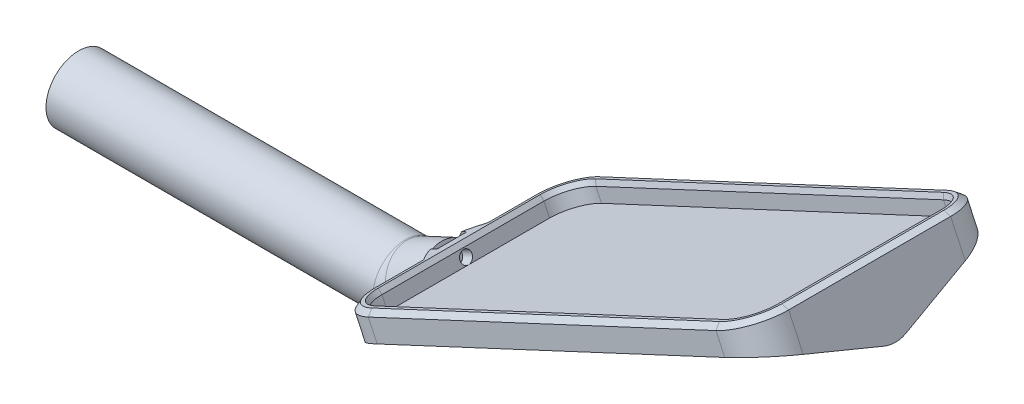
SolidWorks part; units mm, degrees
ref_plane "Alzado" through (0, 0, 0) normal (0, 0, 1) x (1, 0, 0)
ref_plane "Planta" through (0, 0, 0) normal (0, 1, 0) x (1, 0, 0)
ref_plane "Vista lateral" through (0, 0, 0) normal (1, 0, 0) x (0, 0, -1)
sketch "Croquis1" plane through (0, 0, 0) normal (1, 0, 0) x (0, 0, -1)
  circle A0 centre (0, 0) radius 9
  dimension "D1" = 18
extrude "Saliente-Extruir1" add sketch "Croquis1" along normal blind 90
sketch "Croquis2" plane through (90, 0, 0) normal (1, 0, 0) x (0, 0, -1)
  line L0 (-18.2788, 10) -> (25.9849, 10) construction
  circle A1 centre (0, 0) radius 9
  circle A2 centre (0, 0) radius 9
  dimension "D1" = 10
  dimension "D2" = 0
revolve "Revolución1" add sketch "Croquis2" angle 25 about L0 reverse direction yes
sketch "Croquis3" plane through (77.7557, 36.2581, 0) normal (0.9063, 0.4226, 0) x (0, 0, -1)
  circle A1 centre (0, -38.9726) radius 9
  circle A2 centre (0, -38.9726) radius 9
  dimension "D1" = 0
extrude "Saliente-Extruir2" add sketch "Croquis3" along normal blind 140
sketch "Croquis5" plane through (204.6388, 95.4246, 0) normal (0.9063, 0.4226, 0) x (0, 0, -1)
  line L0 (-32.8, -36.8226) -> (-3.0251, -47.4489)
  line L1 (-32.8, -29.8226) -> (32.8, -29.8226)
  line L2 (-32.8, -29.8226) -> (-32.8, -36.8226)
  line L4 (32.8, -29.8226) -> (32.8, -36.8226)
  line L5 (32.8, -36.8226) -> (3.0251, -47.4489)
  circle A1 centre (0, -38.9726) radius 9
  arc A2 (-3.0251, -47.4489) -> (3.0251, -47.4489) centre (0, -38.9726) ccw
  point P7 (0, -29.8226)
  dimension "D2" = 65.6
  dimension "D3" = 7
  dimension "D1" = 0
extrude "Saliente-Extruir3" add sketch "Croquis5" against normal blind 126.6
sketch "Croquis7" plane through (12.6036, -27.0285, 0) normal (-0.4226, 0.9063, 0) x (0.9063, 0.4226, 0)
  line L1 (102.1939, 29.8) -> (222.7939, 29.8)
  line L2 (102.1939, 29.8) -> (102.1939, -29.8)
  line L3 (102.1939, -29.8) -> (222.7939, -29.8)
  line L4 (222.7939, 29.8) -> (222.7939, -29.8)
  line L6 (99.1939, 9) -> (99.1939, -9) construction
  line L7 (99.1939, 32.8) -> (225.7939, 32.8) construction
  point P4 (102.1939, 0)
  point P8 (99.1939, 0)
  point P11 (162.4939, 29.8)
  point P12 (162.4939, 32.8)
  dimension "D1" = 59.6
  dimension "D2" = 120.6
extrude "Cortar-Extruir1" cut sketch "Croquis7" against normal blind 5
fillet "Redondeo2" radius 7.5 4 edges at (215.58, 64.8625, 29.8) (215.58, 64.8625, -29.8) (106.2792, 13.8947, -29.8) (106.2792, 13.8947, 29.8)
fillet "Redondeo1" radius 10.5 4 edges at (218.7215, 65.2241, -32.8) (103.9829, 11.7206, -32.8) (103.9829, 11.7206, 32.8) (218.7215, 65.2241, 32.8)
sketch "Croquis8" plane through (92.6191, 43.189, 0) normal (0.9063, 0.4226, 0) x (0, 0, -1)
  line L0 (22.3, -34.8226) -> (-22.3, -34.8226) construction
  circle A0 centre (0, -33.1726) radius 1.65
  point P2 (0, 0)
  point P5 (0, -34.8226)
  point P6 (0, -32.4635)
  dimension "D1" = 3.3
extrude "Cortar-Extruir2" cut sketch "Croquis8" against normal blind 60
sketch "Croquis9" plane through (12.6036, -27.0285, 0) normal (-0.4226, 0.9063, 0) x (0.9063, 0.4226, 0)
  line L1 (96.1939, 4.3936) -> (99.1939, 4.3936)
  line L2 (96.1939, 4.3936) -> (96.1939, -3.8064)
  line L3 (96.1939, -3.8064) -> (99.1939, -3.8064)
  line L4 (99.1939, 4.3936) -> (99.1939, -3.8064)
  line L5 (99.1939, 22.3) -> (99.1939, -22.3) construction
  dimension "D1" = 8.2
  dimension "D2" = 3
extrude "Cortar-Extruir3" cut sketch "Croquis9" against normal blind 7.6
chamfer "Chaflán1" distance 3 angle 40 2 edges at (106.6883, 5.9189, -8.9686) (106.5492, 6.2173, 8.9901) first distance on face at (94.2262, 0.9369, -9)
sketch "Croquis10" plane through (89.9002, 41.9211, 0) normal (-0.9063, -0.4226, 0) x (0, 0, 1)
  circle A2 centre (0, -33.1726) radius 3.05
  dimension "D1" = 6.1
extrude "Cortar-Extruir4" cut sketch "Croquis10" along normal blind 58.6 from offset 20
chamfer "Chaflán2" distance 1.5 angle 40 9 edges at (102.5038, 14.8927, 14.6474) (105.291, 16.1924, 29.7246) (159.8731, 41.6444, 32.8) (214.4551, 67.0964, 29.7246) (102.5038, 14.8927, -14.6474) (217.2423, 68.3961, 0) (105.291, 16.1924, -29.7246) (214.4551, 67.0964, -29.7246) (159.8731, 41.6444, -32.8) first distance on face at (159.8731, 41.6444, 0)
chamfer "Chaflán3" distance 0.5 angle 70 8 edges at (105.2227, 16.1605, 0) (107.2136, 17.0889, 27.6033) (107.2136, 17.0889, -27.6033) (159.8731, 41.6444, 29.8) (159.8731, 41.6444, -29.8) (212.5325, 66.1999, 27.6033) (212.5325, 66.1999, -27.6033) (214.5234, 67.1283, 0) first distance on face at (135.2686, 30.1711, -0.0629)
